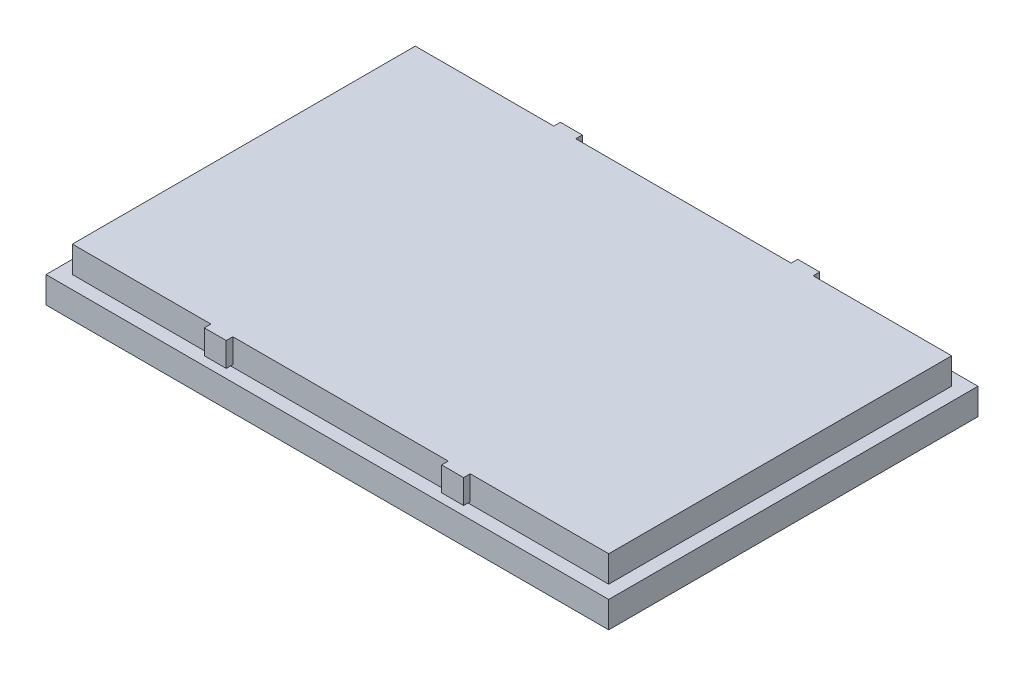
SolidWorks part; units mm, degrees
ref_plane "Front Plane" through (0, 0, 0) normal (0, 0, 1) x (1, 0, 0)
ref_plane "Top Plane" through (0, 0, 0) normal (0, 1, 0) x (1, 0, 0)
ref_plane "Right Plane" through (0, 0, 0) normal (1, 0, 0) x (0, 0, -1)
sketch "Sketch1" plane through (0, 0, 0) normal (0, 0, 1) x (1, 0, 0)
  line L1 (14, 0) -> (39.6, 0)
  line L2 (14, 0) -> (14, 1.2)
  line L3 (14, 1.2) -> (39.6, 1.2)
  line L4 (39.6, 0) -> (39.6, 1.2)
extrude "Boss-Extrude1" add sketch "Sketch1" along normal blind 16.8 from offset 72.4 offset against normal yes
sketch "Sketch2" plane through (0, 0, 0) normal (0, 0, 1) x (1, 0, 0)
  line L1 (14.6, 1.19) -> (39, 1.19)
  line L2 (14.6, 1.19) -> (14.6, 2.4)
  line L3 (14.6, 2.4) -> (39, 2.4)
  line L4 (39, 1.19) -> (39, 2.4)
extrude "Boss-Extrude2" add sketch "Sketch2" along normal blind 15.6 from offset 71.8 offset against normal yes
sketch "Sketch3" plane through (0, 0, 0) normal (0, 0, 1) x (1, 0, 0)
  line L1 (20.9, 1.3) -> (21.9, 1.3)
  line L2 (20.9, 1.3) -> (20.9, 2.4)
  line L3 (20.9, 2.4) -> (21.9, 2.4)
  line L4 (21.9, 1.3) -> (21.9, 2.4)
extrude "Boss-Extrude3" add sketch "Sketch3" along normal blind 0.31 from offset 72.1 offset against normal yes
sketch "Sketch4" plane through (0, 0, 0) normal (0, 0, 1) x (1, 0, 0)
  line L1 (20.9, 1.3) -> (21.9, 1.3)
  line L2 (20.9, 1.3) -> (20.9, 2.4)
  line L3 (20.9, 2.4) -> (21.9, 2.4)
  line L4 (21.9, 1.3) -> (21.9, 2.4)
extrude "Boss-Extrude4" add sketch "Sketch4" along normal blind 0.31 from offset 56.21 offset against normal yes
sketch "Sketch5" plane through (0, 0, 0) normal (0, 0, 1) x (1, 0, 0)
  line L1 (31.7, 1.3) -> (32.7, 1.3)
  line L2 (31.7, 1.3) -> (31.7, 2.4)
  line L3 (31.7, 2.4) -> (32.7, 2.4)
  line L4 (32.7, 1.3) -> (32.7, 2.4)
extrude "Boss-Extrude5" add sketch "Sketch5" along normal blind 0.31 from offset 72.1 offset against normal yes
sketch "Sketch6" plane through (0, 0, 0) normal (0, 0, 1) x (1, 0, 0)
  line L1 (31.7, 1.3) -> (32.7, 1.3)
  line L2 (31.7, 1.3) -> (31.7, 2.4)
  line L3 (31.7, 2.4) -> (32.7, 2.4)
  line L4 (32.7, 1.3) -> (32.7, 2.4)
extrude "Boss-Extrude6" add sketch "Sketch6" along normal blind 0.31 from offset 56.21 offset against normal yes
sketch "Sketch7" plane through (0, 0, 0) normal (0, 0, 1) x (1, 0, 0)
  line L1 (25.3, -0.1) -> (28.3, -0.1)
  line L2 (25.3, -0.1) -> (25.3, 0.6)
  line L3 (25.3, 0.6) -> (28.3, 0.6)
  line L4 (28.3, -0.1) -> (28.3, 0.6)
extrude "Boss-Extrude7" add sketch "Sketch7" along normal blind 0.9 from offset 72.5 separate body offset against normal yes
combine bodies "Combine1" operation type subtract main body 106 bodies to subtract 107
